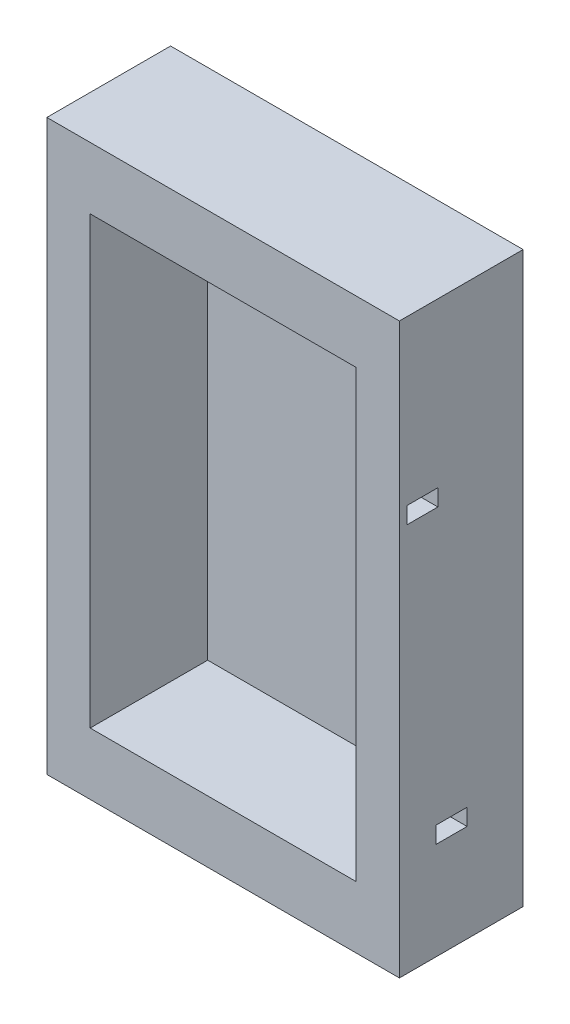
SolidWorks part; units mm, degrees
ref_plane "Front Plane" through (0, 0, 0) normal (0, 0, 1) x (1, 0, 0)
ref_plane "Top Plane" through (0, 0, 0) normal (0, 1, 0) x (1, 0, 0)
ref_plane "Right Plane" through (0, 0, 0) normal (1, 0, 0) x (0, 0, -1)
sketch "Sketch1" plane through (0, 0, 0) normal (0, 0, 1) x (1, 0, 0)
  line L1 (72.39, -116.84) -> (-72.39, -116.84)
  line L2 (72.39, -116.84) -> (72.39, 116.84)
  line L3 (72.39, 116.84) -> (-72.39, 116.84)
  line L4 (-72.39, -116.84) -> (-72.39, 116.84)
  line L5 (72.39, -116.84) -> (-72.39, 116.84) construction
  line L6 (72.39, 116.84) -> (-72.39, -116.84) construction
  point P0 (0, 0)
  dimension "D1" = 144.78
  dimension "D2" = 233.68
extrude "Boss-Extrude1" add sketch "Sketch1" along normal blind 50.8
sketch "Sketch2" plane through (0, 0, 50.8) normal (0, 0, 1) x (1, 0, 0)
  line L1 (54.61, -91.44) -> (-54.61, -91.44)
  line L2 (54.61, -91.44) -> (54.61, 91.44)
  line L3 (54.61, 91.44) -> (-54.61, 91.44)
  line L4 (-54.61, -91.44) -> (-54.61, 91.44)
  line L5 (54.61, -91.44) -> (-54.61, 91.44) construction
  line L6 (54.61, 91.44) -> (-54.61, -91.44) construction
  point P0 (0, 0)
  dimension "D1" = 109.22
  dimension "D2" = 182.88
extrude "Cut-Extrude1" cut sketch "Sketch2" against normal blind 48.26
sketch "Sketch6" plane through (72.39, 0, 0) normal (1, 0, 0) x (0, 0, -1)
  line L0 (-41.35, 46.215) -> (-29.35, -73.415) construction
  line L1 (-47.7, 49.64) -> (-35, 49.64)
  line L2 (-47.7, 49.64) -> (-47.7, 42.79)
  line L3 (-47.7, 42.79) -> (-35, 42.79)
  line L4 (-35, 49.64) -> (-35, 42.79)
  line L5 (-47.7, 49.64) -> (-35, 42.79) construction
  line L6 (-47.7, 42.79) -> (-35, 49.64) construction
  line L12 (-23, -69.99) -> (-35.7, -69.99)
  line L13 (-23, -69.99) -> (-23, -76.84)
  line L14 (-23, -76.84) -> (-35.7, -76.84)
  line L15 (-35.7, -69.99) -> (-35.7, -76.84)
  line L16 (-23, -69.99) -> (-35.7, -76.84) construction
  line L17 (-23, -76.84) -> (-35.7, -69.99) construction
  line L18 (-50.8, 116.84) -> (0, 116.84) construction
  line L19 (0, -116.84) -> (0, 116.84) construction
  line L20 (-50.8, -116.84) -> (0, -116.84) construction
  point P0 (-41.35, 46.215)
  point P5 (-22.8614, -57.2611)
  dimension "D1" = 6.85
  dimension "D2" = 12.7
  dimension "D3" = 12.7
  dimension "D4" = 6.85
  dimension "D5" = 67.2
  dimension "D6" = 35
  dimension "D7" = 40
  dimension "D8" = 23
extrude "Cut-Extrude3" cut sketch "Sketch6" against normal up to next
